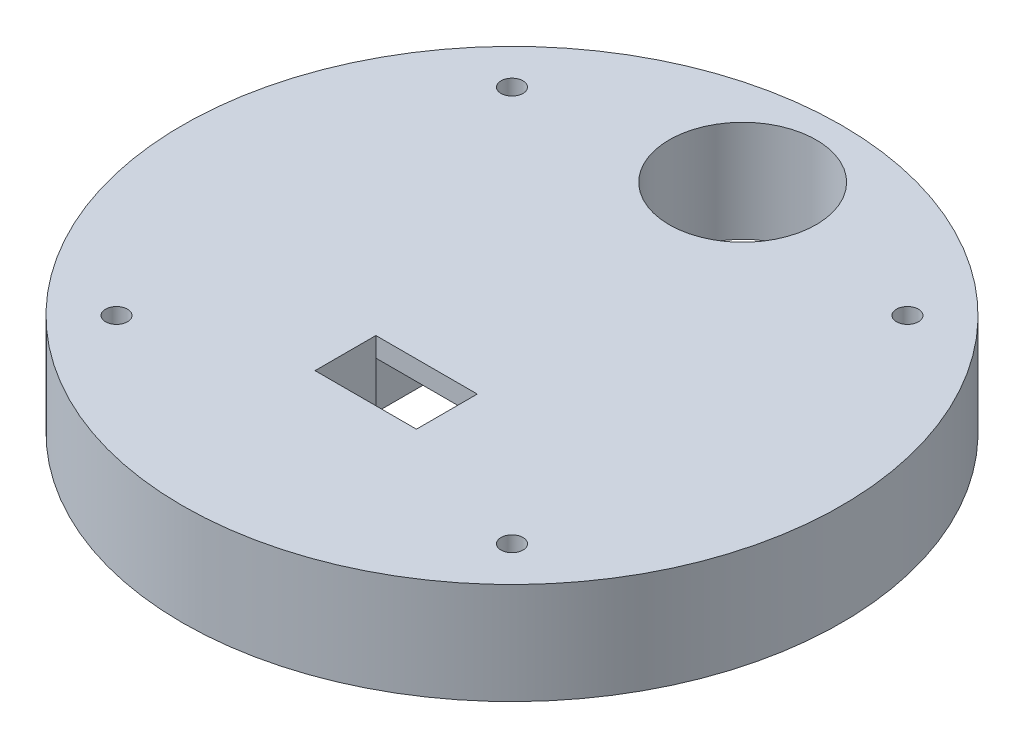
SolidWorks part; units mm, degrees
ref_plane "Front Plane" through (0, 0, 0) normal (0, 0, 1) x (1, 0, 0)
ref_plane "Top Plane" through (0, 0, 0) normal (0, 1, 0) x (1, 0, 0)
ref_plane "Right Plane" through (0, 0, 0) normal (1, 0, 0) x (0, 0, -1)
sketch "Sketch1" plane through (0, 0, 0) normal (0, 1, 0) x (1, 0, 0)
  line L1 (57.15, 57.15) -> (-57.15, 57.15) construction
  line L2 (57.15, 57.15) -> (57.15, -57.15) construction
  line L3 (57.15, -57.15) -> (-57.15, -57.15) construction
  line L4 (-57.15, 57.15) -> (-57.15, -57.15) construction
  line L5 (57.15, 57.15) -> (-57.15, -57.15) construction
  line L6 (57.15, -57.15) -> (-57.15, 57.15) construction
  line L7 (21.3995, 21.3995) -> (-21.3995, 21.3995)
  line L8 (21.3995, 21.3995) -> (21.3995, -21.3995)
  line L9 (21.3995, -21.3995) -> (-21.3995, -21.3995)
  line L10 (-21.3995, 21.3995) -> (-21.3995, -21.3995)
  line L11 (21.3995, 21.3995) -> (-21.3995, -21.3995) construction
  line L12 (21.3995, -21.3995) -> (-21.3995, 21.3995) construction
  circle A0 centre (-49.53, 49.53) radius 2.75
  circle A1 centre (49.53, 49.53) radius 2.75
  circle A2 centre (49.53, -49.53) radius 2.75
  circle A3 centre (-49.53, -49.53) radius 2.75
  circle A4 centre (0, 0) radius 82.55
  circle A6 centre (0, 57.785) radius 18.415
  circle A7 centre (0, 0) radius 76.2
  point P0 (0, 0)
  point P14 (0, 0)
  dimension "D4" = 5.5
  dimension "D6" = 165.1
  dimension "D7" = 36.83
  dimension "D10" = 152.4
  dimension "D1" = 99.06
  dimension "D2" = 99.06
  dimension "D3" = 114.3
  dimension "D5" = 42.799
extrude "Boss-Extrude3" add sketch "Sketch1" along normal blind 25.4 contours A7 | A4 A7 | A7 A3 A2 A1 A0 L10 L7 L8 L9 | L7 L10 L9 L8 | A0 | A1 | A2 | A3 region at (0, 0, 0) region at (-49.53, 0, -49.53) region at (49.53, 0, -49.53) region at (49.53, 0, 49.53) region at (-49.53, 0, 49.53) region at (-80.2151, 0, 0) region at (52.3575, 0, -52.3575)
extrude "Cut-Extrude2" cut sketch "Sketch1<7>" along normal blind 20.5 contours L7 L10 L9 L8 region at (0, 0, 0)
sketch "Sketch1<7>" plane through (0, 0, 0) normal (0, 1, 0) x (1, 0, 0) same geometry as "Sketch1"
sketch "Sketch3" plane through (0, 0, 0) normal (0, -1, 0) x (1, 0, 0)
  line L0 (21.3995, 21.3995) -> (-21.3995, 21.3995) construction
  line L1 (-12.7, 21.3995) -> (12.7, 21.3995)
  line L2 (-12.7, 21.3995) -> (-12.7, 36.6395)
  line L3 (-12.7, 36.6395) -> (12.7, 36.6395)
  line L4 (12.7, 21.3995) -> (12.7, 36.6395)
  line L5 (0, 36.6395) -> (0, 0) construction
  dimension "1" = 25.4
  dimension "D2" = 15.24
extrude "Cut-Extrude3" cut sketch "Sketch3" against normal through all
extrude "Cut-Extrude4" cut sketch "Sketch1<8>" along normal blind 6 contours A3 | A2 | A0 | A1 region at (-49.53, 0, -49.53) region at (49.53, 0, -49.53) region at (49.53, 0, 49.53) region at (-49.53, 0, 49.53)
sketch "Sketch1<8>" plane through (0, 0, 0) normal (0, 1, 0) x (1, 0, 0) same geometry as "Sketch1"
extrude "Cut-Extrude5" cut sketch "Sketch1<10>" against normal blind 6 from offset 25.4 contours A0 | A1 | A3 | A2 region at (-49.53, 0, -49.53) region at (49.53, 0, -49.53) region at (49.53, 0, 49.53) region at (-49.53, 0, 49.53)
sketch "Sketch1<10>" plane through (0, 0, 0) normal (0, 1, 0) x (1, 0, 0) same geometry as "Sketch1"
